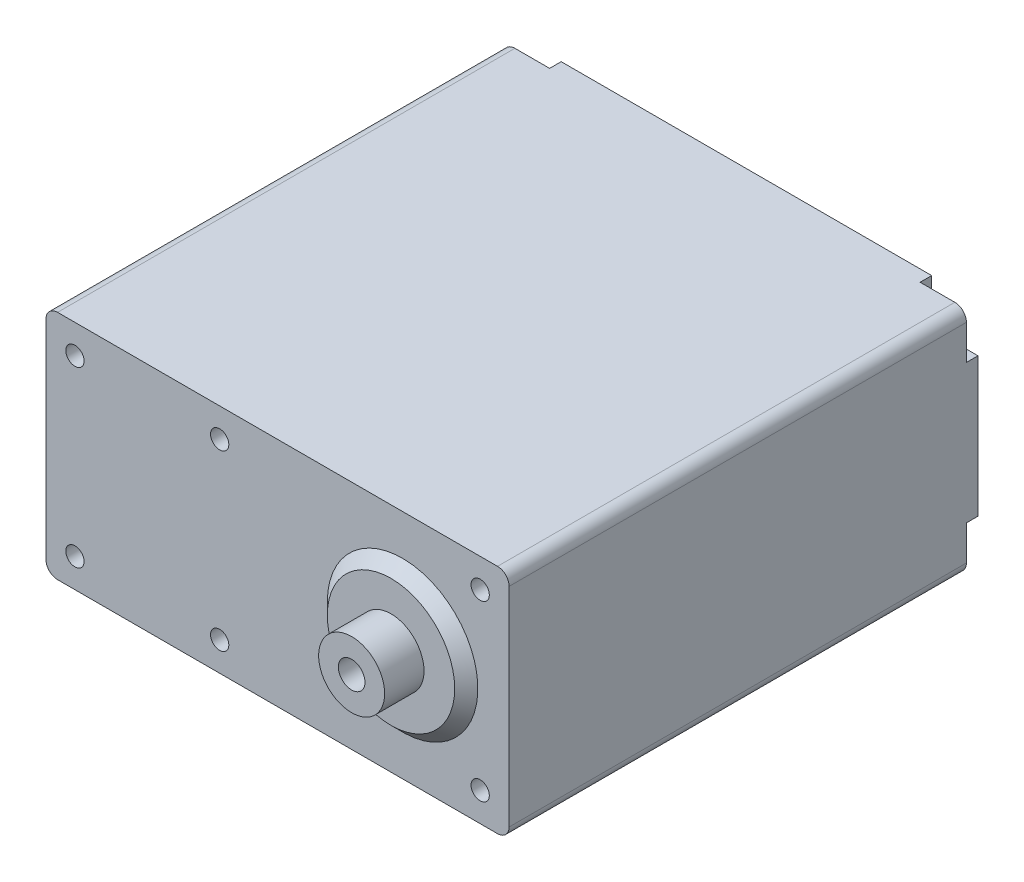
SolidWorks part; units mm, degrees
ref_plane "Plan de face" through (0, 0, 0) normal (0, 0, 1) x (1, 0, 0)
ref_plane "Plan de dessus" through (0, 0, 0) normal (0, 1, 0) x (1, 0, 0)
ref_plane "Plan de droite" through (0, 0, 0) normal (1, 0, 0) x (0, 0, -1)
sketch "Esquisse1" plane through (0, 0, 0) normal (0, 0, 1) x (1, 0, 0)
  line L1 (0, 0) -> (40, 0)
  line L2 (0, 0) -> (0, 20)
  line L3 (0, 20) -> (40, 20)
  line L4 (40, 0) -> (40, 20)
  dimension "D1" = 40
  dimension "D2" = 20
extrude "Boss.-Extru.1" add sketch "Esquisse1" along normal blind 40.5
sketch "Esquisse2" plane through (0, 0, 0) normal (0, 0, -1) x (-1, 0, 0)
  line L0 (-2.5, -5.9821) -> (-2.5, 29.3399) construction
  line L1 (0, 20) -> (0, 0) construction
  line L2 (2.5402, 2.5) -> (-47.4461, 2.5) construction
  line L3 (5.01, 17.5) -> (-49.3253, 17.5) construction
  line L4 (0, 0) -> (-40, 0) construction
  line L6 (-37.5, -7.5487) -> (-37.5, 29.8462) construction
  line L7 (-40, 0) -> (-40, 20) construction
  circle A0 centre (-2.5, 2.5) radius 0.79
  circle A2 centre (-37.5, 2.5) radius 0.79
  circle A3 centre (-2.5, 17.5) radius 0.79
  circle A5 centre (-37.5, 17.5) radius 0.79
  dimension "D1" = 1.58
  dimension "D2" = 1.58
  dimension "D4" = 1.58
  dimension "D6" = 1.58
  dimension "D7" = 2.5
  dimension "D8" = 15
  dimension "D9" = 2.5
  dimension "D11" = 2.5
extrude "Enlèv. mat.-Extru.2" cut sketch "Esquisse2" against normal through all
sketch "Esquisse3" plane through (0, 0, 0) normal (0, 0, -1) x (-1, 0, 0)
  line L0 (-40, 20) -> (0, 20) construction
  line L1 (0, 16) -> (-3, 16)
  line L2 (0, 16) -> (0, 20)
  line L3 (0, 20) -> (-4, 20)
  line L4 (-4, 17) -> (-4, 20)
  line L5 (0, 20) -> (0, 0) construction
  line L6 (0, 0) -> (-40, 0) construction
  line L7 (0, 0) -> (-4, 0)
  line L8 (0, 0) -> (0, 4)
  line L9 (0, 4) -> (-3, 4)
  line L10 (-4, 0) -> (-4, 3)
  line L11 (-40, 0) -> (-40, 20) construction
  line L12 (-36, 0) -> (-40, 0)
  line L13 (-36, 0) -> (-36, 3)
  line L14 (-37, 4) -> (-40, 4)
  line L15 (-40, 0) -> (-40, 4)
  line L16 (-37, 16) -> (-40, 16)
  line L17 (-36, 17) -> (-36, 20)
  line L18 (-36, 20) -> (-40, 20)
  line L19 (-40, 16) -> (-40, 20)
  arc A0 (-4, 3) -> (-3, 4) centre (-3, 3) cw
  arc A1 (-37, 4) -> (-36, 3) centre (-37, 3) cw
  arc A2 (-36, 17) -> (-37, 16) centre (-37, 17) cw
  arc A3 (-4, 17) -> (-3, 16) centre (-3, 17) ccw
  point P26 (-4, 4)
  point P29 (-36, 4)
  point P32 (-36, 16)
  point P35 (-4, 16)
  dimension "D9" = 1
  dimension "D10" = 1
  dimension "D1" = 4
  dimension "D2" = 4
  dimension "D3" = 4
  dimension "D4" = 4
  dimension "D5" = 4
  dimension "D6" = 4
  dimension "D7" = 4
  dimension "D8" = 4
extrude "Enlèv. mat.-Extru.3" cut sketch "Esquisse3" against normal blind 1
sketch "Esquisse4" plane through (0, 0, 0) normal (0, 0, -1) x (-1, 0, 0)
  line L0 (46.8485, 10) -> (-52.8485, 10) construction
  line L1 (-3, -6.7566) -> (-3, 29.0278) construction
  line L2 (-10, -6.3135) -> (-10, 29.0278) construction
  line L3 (-4, 0) -> (-36, 0) construction
  line L4 (0, 16) -> (0, 4) construction
  line L5 (28.5707, 17) -> (-48.5707, 17) construction
  line L6 (1.301, 3) -> (-49.2244, 3) construction
  line L7 (-17, -2.433) -> (-17, 22.0047) construction
  line L8 (4.7758, 18) -> (-58.8613, 18) construction
  line L9 (4.0048, 2) -> (-51.9874, 2) construction
  line L10 (-24, -2.8253) -> (-24, 26.0851) construction
  line L11 (-40, 4) -> (-40, 16) construction
  circle A0 centre (-3, 10) radius 0.79
  circle A1 centre (-10, 17) radius 0.79
  circle A2 centre (-10, 3) radius 0.79
  circle A3 centre (-17, 10) radius 0.79
  circle A4 centre (-24, 2) radius 0.79
  circle A5 centre (-24, 18) radius 0.79
  dimension "D6" = 1.58
  dimension "D7" = 1.58
  dimension "D8" = 1.58
  dimension "D9" = 1.58
  dimension "D14" = 1.58
  dimension "D15" = 1.58
  dimension "D1" = 10
  dimension "D2" = 3
  dimension "D3" = 7
  dimension "D4" = 7
  dimension "D5" = 14
  dimension "D10" = 7
  dimension "D11" = 16
  dimension "D12" = 8
  dimension "D13" = 16
extrude "Enlèv. mat.-Extru.4" cut sketch "Esquisse4" against normal blind 20
sketch "Esquisse5" plane through (0, 0, 0) normal (0, 0, -1) x (-1, 0, 0)
  line L0 (-24, -3.6753) -> (-24, 24.9448) construction
  line L1 (3.6193, 10) -> (-44.2348, 10) construction
  line L2 (-30.8, -5.0217) -> (-30.8, 25.3295) construction
  line L3 (2.2345, 2) -> (-45.6196, 2) construction
  line L4 (2.6961, 18) -> (-45.6196, 18) construction
  line L5 (-4, 0) -> (-36, 0) construction
  line L6 (-40, 4) -> (-40, 16) construction
  circle A0 centre (-30.8, 10) radius 6.5
  dimension "D6" = 13
  dimension "D1" = 10
  dimension "D2" = 8
  dimension "D3" = 16
  dimension "D4" = 6.8
  dimension "D5" = 16
extrude "Boss.-Extru.2" add sketch "Esquisse5" along normal blind 1
chamfer "Chanfrein1" distance 1 angle 45 1 edges at (24.3, 10, -1)
sketch "Esquisse6" plane through (0, 0, -1) normal (0, 0, -1) x (-1, 0, 0)
  line L0 (4.6195, 10) -> (-46.8121, 10) construction
  line L1 (-30.8, -4.8294) -> (-30.8, 25.4449) construction
  line L2 (-4, 0) -> (-36, 0) construction
  line L3 (-40, 4) -> (-40, 16) construction
  circle A0 centre (-30.8, 10) radius 2.85
  dimension "D3" = 5.7
  dimension "D1" = 10
  dimension "D2" = 9.2
extrude "Boss.-Extru.3" add sketch "Esquisse6" along normal blind 3.4
fillet "Congé1" radius 1 4 edges at (0, 0, 20.75) (40, 0, 20.75) (40, 20, 20.75) (0, 20, 20.75)
sketch "Esquisse7" plane through (0, 0, 40.5) normal (0, 0, 1) x (1, 0, 0)
  line L0 (43.3116, 10) -> (-5.5812, 10) construction
  line L1 (30.8, -3.5599) -> (30.8, 26.1758) construction
  line L2 (1, 0) -> (39, 0) construction
  line L3 (40, 1) -> (40, 19) construction
  circle A0 centre (30.8, 10) radius 6.5
  dimension "D1" = 13
  dimension "D2" = 10
  dimension "D3" = 9.2
extrude "Boss.-Extru.4" add sketch "Esquisse7" along normal blind 1
chamfer "Chanfrein2" distance 1 angle 45 1 edges at (37.3, 10, 41.5)
sketch "Esquisse8" plane through (0, 0, 41.5) normal (0, 0, 1) x (1, 0, 0)
  line L0 (42.1575, 10) -> (-4.2733, 10) construction
  line L1 (30.8, -3.9446) -> (30.8, 25.1756) construction
  line L2 (40, 1) -> (40, 19) construction
  line L3 (1, 0) -> (39, 0) construction
  circle A0 centre (30.8, 10) radius 2.85
  dimension "D3" = 5.7
  dimension "D1" = 9.2
  dimension "D2" = 10
extrude "Boss.-Extru.5" add sketch "Esquisse8" along normal blind 3.4
sketch "Esquisse9" plane through (0, 0, 0) normal (0, -1, 0) x (1, 0, 0)
  line L1 (30.8522, 30.3894) -> (25.8522, 30.3894)
  line L2 (31.8522, 31.3894) -> (31.8522, 33.3894)
  line L3 (30.8522, 34.3894) -> (25.8522, 34.3894)
  line L4 (24.8522, 31.3894) -> (24.8522, 33.3894)
  arc A0 (31.8522, 33.3894) -> (30.8522, 34.3894) centre (30.8522, 33.3894) ccw
  arc A1 (24.8522, 33.3894) -> (25.8522, 34.3894) centre (25.8522, 33.3894) cw
  arc A2 (25.8522, 30.3894) -> (24.8522, 31.3894) centre (25.8522, 31.3894) cw
  arc A3 (30.8522, 30.3894) -> (31.8522, 31.3894) centre (30.8522, 31.3894) ccw
  point P6 (31.8522, 34.3894)
  point P11 (24.8522, 30.3894)
  point P14 (31.8522, 30.3894)
  dimension "D3" = 1
  dimension "D1" = 7
  dimension "D2" = 4
extrude "Enlèv. mat.-Extru.6" cut sketch "Esquisse9" against normal blind 15
sketch "Esquisse10" plane through (0, 0, 40.5) normal (0, 0, 1) x (1, 0, 0)
  line L0 (-3.0038, 10) -> (44.1194, 10) construction
  line L1 (15, -3.1368) -> (15, 23.9062) construction
  line L2 (-4.8118, 17.5) -> (44.7349, 17.5) construction
  line L3 (1, 0) -> (39, 0) construction
  line L4 (0, 19) -> (0, 1) construction
  line L5 (-6.0043, 2.5) -> (47.7738, 2.5) construction
  circle A0 centre (15, 2.5) radius 0.79
  circle A1 centre (15, 17.5) radius 0.79
  dimension "D4" = 1.58
  dimension "D5" = 1.58
  dimension "D1" = 10
  dimension "D2" = 15
  dimension "D3" = 7.5
  dimension "D6" = 15
extrude "Enlèv. mat.-Extru.7" cut sketch "Esquisse10" against normal blind 20
sketch "Esquisse11" plane through (0, 0, 44.9) normal (0, 0, 1) x (1, 0, 0)
  circle A0 centre (30.8, 10) radius 1.15
  circle A1 centre (30.8, 10) radius 2.85 construction
  dimension "D1" = 2.3
extrude "Enlèv. mat.-Extru.8" cut sketch "Esquisse11" against normal blind 15
sketch "Esquisse12" plane through (0, 0, -4.4) normal (0, 0, -1) x (-1, 0, 0)
  circle A0 centre (-30.8, 10) radius 1.15
  circle A1 centre (-30.8, 10) radius 2.85 construction
  dimension "D1" = 2.3
extrude "Enlèv. mat.-Extru.9" cut sketch "Esquisse12" against normal blind 15
